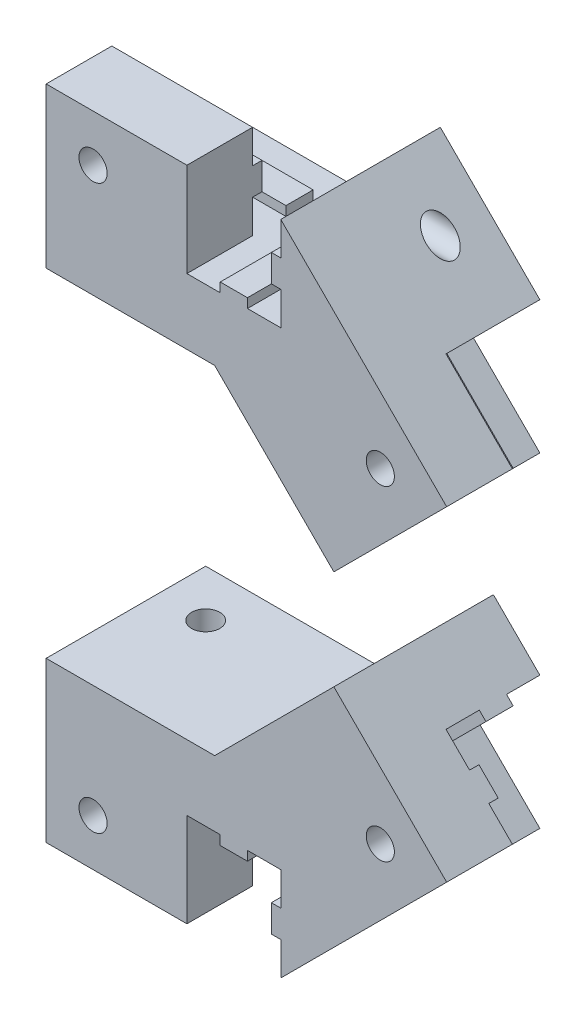
SolidWorks part; units mm, degrees
ref_plane "Front Plane" through (0, 0, 0) normal (0, 0, 1) x (1, 0, 0)
ref_plane "Top Plane" through (0, 0, 0) normal (0, 1, 0) x (1, 0, 0)
ref_plane "Right Plane" through (0, 0, 0) normal (1, 0, 0) x (0, 0, -1)
ref_plane "FrontPlane+10mm" through (0, 0, 10) normal (0, 0, 1) x (1, 0, 0)
sketch "Sketch1" plane through (0, 0, 0) normal (0, 0, 1) x (1, 0, 0)
  line L0 (-290, 0) -> (-10, 0) construction
  line L1 (0, 0) -> (-90, -90) construction
  line L2 (-10, 0) -> (0, 0) construction
  line L3 (-10, 0) -> (-10, 10) construction
  line L4 (-10, 10) -> (0, 10) construction
  line L5 (0, 0) -> (0, 10) construction
  line L6 (-90, -90) -> (-210, -90) construction
  line L7 (-300, 10) -> (-290, 10) construction
  line L8 (-300, 10) -> (-300, 0) construction
  line L9 (-90, -90) -> (-72.3223, -72.3223)
  line L10 (-290, 10) -> (-290, 0) construction
  line L11 (-210, -90) -> (-300, 0) construction
  line L12 (-88.1335, -73.9914) -> (-16.0086, -1.8665) construction
  line L13 (-115, -80) -> (-90, -80) construction
  line L14 (-115, -80) -> (-115, -90) construction
  line L15 (-90, -90) -> (-90, -80)
  line L16 (-90, -80) -> (-90, -90) construction
  line L17 (-16.0086, -1.8665) -> (-8.9376, -8.9376) construction
  line L18 (-88.1335, -73.9914) -> (-81.0624, -81.0624) construction
  line L19 (-16.0086, -1.8665) -> (0, 0) construction
  line L20 (-88.1335, -73.9914) -> (-90, -90) construction
  line L21 (-90, -80) -> (-115, -80)
  line L22 (-115, -80) -> (-115, -73)
  line L23 (-115, -73) -> (-97.0416, -73)
  line L24 (-97.0416, -73) -> (-84.3431, -60.3015)
  line L25 (-84.3431, -60.3015) -> (-72.3223, -72.3223)
  dimension "D1" = 10
  dimension "D2" = 10
  dimension "D3" = 300
  dimension "D4" = 10
  dimension "D5" = 120
  dimension "D6" = 135
  dimension "D7" = 45
  dimension "D8" = 45
  dimension "D9" = 127.2792
  dimension "D10" = 7
  dimension "D11" = 10
  dimension "D12" = 10
  dimension "D13" = 102
  dimension "D14" = 25
  dimension "D15" = 7
  dimension "D16" = 25
  dimension "D17" = 90
extrude "Main" add sketch "Sketch1" along normal blind 17
sketch "Sketch2" plane through (-72.3223, -72.3223, 0) normal (0.7071, 0.7071, 0) x (0.7071, -0.7071, 0)
  line L0 (-3.55, -10) -> (0, -10)
  line L1 (-10, -3.55) -> (-9, -3.55)
  line L2 (-9, -3.55) -> (-9, -6.45)
  line L3 (-9, -6.45) -> (-10, -6.45)
  line L4 (-6.45, -10) -> (-10, -10)
  line L5 (0, 0) -> (-17, 0) construction
  line L6 (-10, 0) -> (0, 0)
  line L7 (0, 0) -> (0, -10)
  line L8 (0, -17) -> (0, 0) construction
  line L10 (-6.45, -10) -> (-6.45, -9)
  line L11 (-6.45, -9) -> (-3.55, -9)
  line L12 (-3.55, -9) -> (-3.55, -10)
  line L13 (-10, -10) -> (-10, -6.45)
  line L15 (-10, -3.55) -> (-10, 0)
  dimension "D1" = 10
  dimension "D2" = 2.9
  dimension "D3" = 3.55
  dimension "D4" = 1
  dimension "D5" = 10
extrude "Cut-Extrude1" cut sketch "Sketch2" against normal blind 10
sketch "Sketch3" plane through (0, 0, 17) normal (0, 0, 1) x (1, 0, 0)
  line L0 (-90, -90) -> (-72.3223, -72.3223) construction
  line L1 (-72.3223, -72.3223) -> (-84.3431, -60.3015) construction
  circle A0 centre (-79.3934, -72.3223) radius 1.5
  dimension "D1" = 3
  dimension "D2" = 5
  dimension "D3" = 5
extrude "Cut-Extrude2" cut sketch "Sketch3" against normal through all
sketch "Sketch4" plane through (0, 0, 10) normal (0, 0, 1) x (1, 0, 0)
  line L0 (-96.45, -80) -> (-96.45, -81)
  line L1 (-115, -80) -> (-90, -80) construction
  line L2 (-96.45, -81) -> (-93.55, -81)
  line L3 (-93.55, -81) -> (-93.55, -80)
  line L4 (-93.55, -80) -> (-96.45, -80)
  line L6 (-90, -80) -> (-90, -90) construction
  line L7 (-90, -86.45) -> (-91, -86.45)
  line L8 (-90, -86.45) -> (-90, -83.55)
  line L9 (-90, -83.55) -> (-91, -83.55)
  line L10 (-91, -86.45) -> (-91, -83.55)
  dimension "D1" = 3.55
  dimension "D2" = 1
  dimension "D3" = 2.9
  dimension "D4" = 3.55
extrude "Boss-Extrude1" add sketch "Sketch4" along normal up to surface (7 mm away) up to face at (-77.8934, -72.3223, 17)
sketch "Sketch5" plane through (0, -80, 0) normal (0, -1, 0) x (1, 0, 0)
  line L0 (-115, 17) -> (-115, 0) construction
  line L1 (-115, 6.45) -> (-100, 6.45)
  line L2 (-115, 6.45) -> (-115, 3.55)
  line L3 (-115, 3.55) -> (-100, 3.55)
  line L4 (-100, 6.45) -> (-100, 3.55)
  line L5 (-115, 0) -> (-90, 0) construction
  dimension "D1" = 2.9
  dimension "D2" = 3.55
  dimension "D3" = 15
extrude "Boss-Extrude2" add sketch "Sketch5" along normal blind 1
sketch "Sketch6" plane through (0, -73, 0) normal (0, 1, 0) x (1, 0, 0)
  line L0 (-115, -17) -> (-115, 0) construction
  line L3 (-97.0416, 0) -> (-115, 0) construction
  circle A0 centre (-110, -5) radius 1.5
  dimension "D1" = 3
  dimension "D2" = 5
  dimension "D3" = 5
extrude "Cut-Extrude3" cut sketch "Sketch6" against normal through all
sketch "Sketch7" plane through (-115, 0, 0) normal (-1, 0, 0) x (0, 0, 1)
  line L0 (17, -80) -> (17, -90)
  line L1 (17, -90) -> (10, -90)
  line L2 (10, -90) -> (10, -86.45)
  line L3 (10, -86.45) -> (9, -86.45)
  line L4 (9, -86.45) -> (9, -83.55)
  line L5 (9, -83.55) -> (10, -83.55)
  line L6 (10, -83.55) -> (10, -80)
  line L7 (17, -80) -> (6.45, -80) construction
  line L8 (10, -80) -> (17, -80)
  line L9 (10, -79.3934) -> (10, -72.3223) construction
  dimension "D1" = 2.9
  dimension "D2" = 1
extrude "Boss-Extrude3" add sketch "Sketch7" against normal blind 15
sketch "Sketch8" plane through (0, 0, 17) normal (0, 0, 1) x (1, 0, 0)
  line L0 (-100, -90) -> (-115, -90) construction
  line L3 (-115, -73) -> (-115, -90) construction
  circle A0 centre (-110, -85) radius 1.5
  dimension "D1" = 3
  dimension "D2" = 5
  dimension "D3" = 5
extrude "Cut-Extrude4" cut sketch "Sketch8" against normal through all
sketch "Sketch9" plane through (-90, 0, 0) normal (-1, 0, 0) x (0, 0, 1)
  line L0 (0, -80) -> (0, -90) construction
  line L1 (17, -90) -> (0, -90) construction
  circle A0 centre (5, -85) radius 1.5
  dimension "D1" = 3
  dimension "D2" = 5
  dimension "D3" = 5
extrude "Cut-Extrude5" cut sketch "Sketch9" against normal through all
ref_plane "Plane2" through (0, -55, 0) normal (0, 1, 0) x (1, 0, 0)
mirror "Mirror2" about plane through (0, -55, 0) normal (0, 1, 0) of bodies 123
